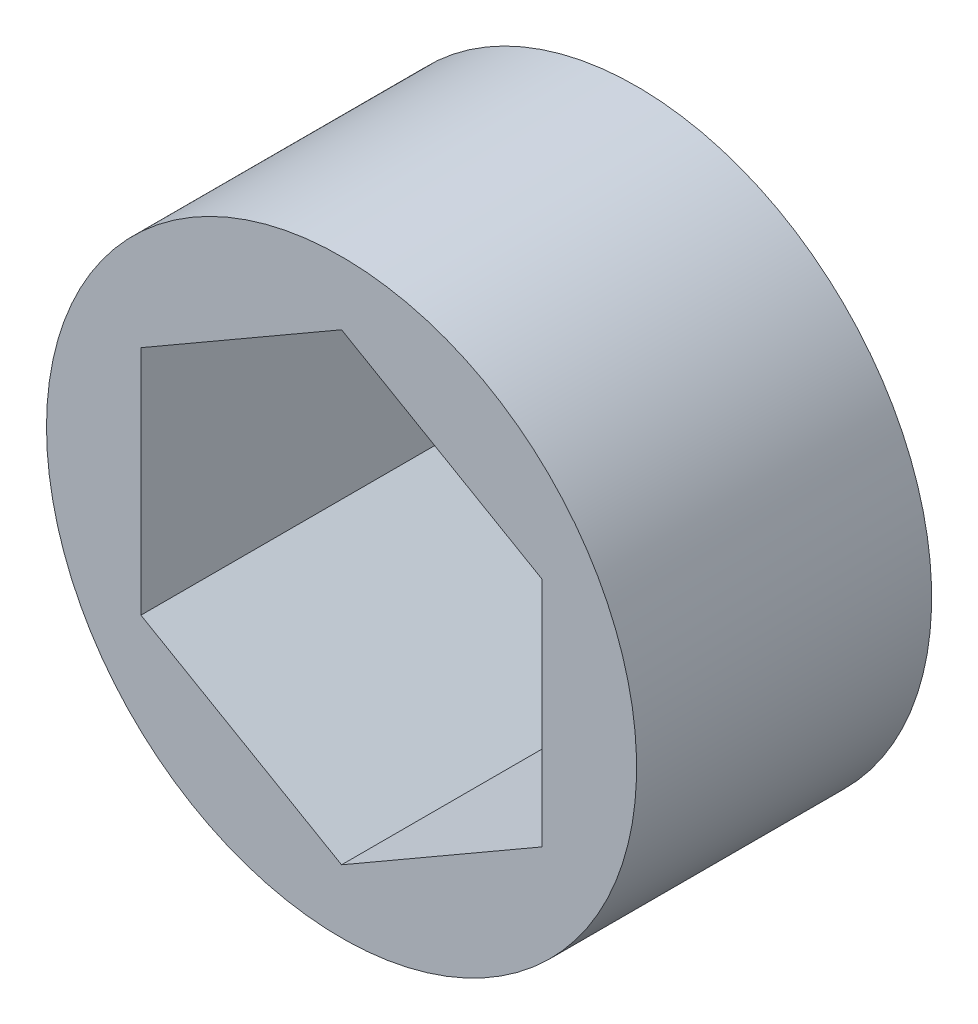
SolidWorks part; units mm, degrees
material "PET"
ref_plane "Front Plane" through (0, 0, 0) normal (0, 0, 1) x (1, 0, 0)
ref_plane "Top Plane" through (0, 0, 0) normal (0, 1, 0) x (1, 0, 0)
ref_plane "Right Plane" through (0, 0, 0) normal (1, 0, 0) x (0, 0, -1)
sketch "Sketch1" plane through (0, 0, 0) normal (0, 0, 1) x (1, 0, 0)
  line L1 (0, 7.479) -> (-6.477, 3.7395)
  line L2 (-6.477, 3.7395) -> (-6.477, -3.7395)
  line L3 (-6.477, -3.7395) -> (0, -7.479)
  line L4 (0, -7.479) -> (6.477, -3.7395)
  line L5 (6.477, -3.7395) -> (6.477, 3.7395)
  line L6 (6.477, 3.7395) -> (0, 7.479)
  circle A0 centre (0, 0) radius 9.525
  circle A1 centre (0, 0) radius 6.477 construction
  dimension "D1" = 19.05
  dimension "D2" = 12.954
extrude "Boss-Extrude1" add sketch "Sketch1" along normal mid plane 9.525
